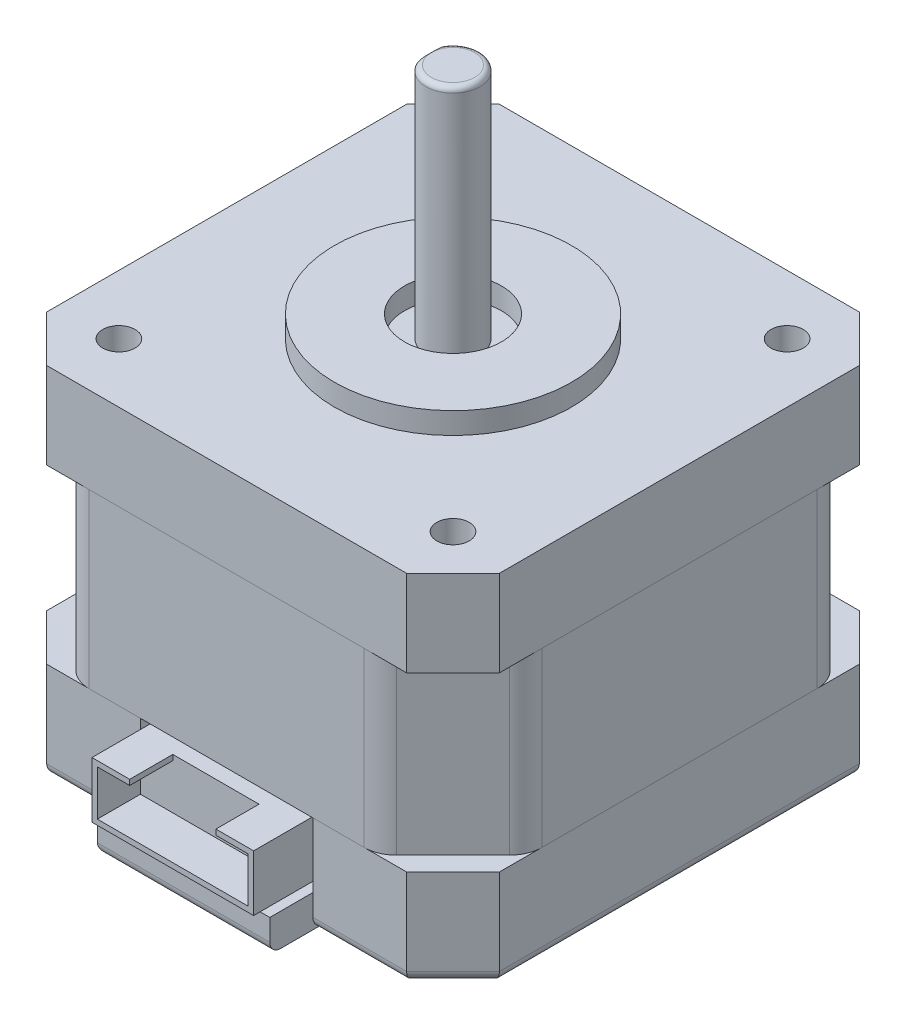
SolidWorks part; units mm, degrees
ref_plane "Front Plane" through (0, 0, 0) normal (0, 0, 1) x (1, 0, 0)
ref_plane "Top Plane" through (0, 0, 0) normal (0, 1, 0) x (1, 0, 0)
ref_plane "Right Plane" through (0, 0, 0) normal (1, 0, 0) x (0, 0, -1)
sketch "Sketch1" plane through (0, 0, 0) normal (0, 1, 0) x (1, 0, 0)
  line L0 (-21, 21) -> (21, -21) construction
  line L1 (-21, 21) -> (21, 21)
  line L2 (-21, 21) -> (-21, -21)
  line L3 (-21, -21) -> (21, -21)
  line L4 (21, 21) -> (21, -21)
  line L5 (-15.5, 15.5) -> (15.5, -15.5) construction
  circle A0 centre (-15.5, 15.5) radius 1.5
  circle A1 centre (15.5, 15.5) radius 1.5
  circle A2 centre (-15.5, -15.5) radius 1.5
  circle A3 centre (15.5, -15.5) radius 1.5
  point P4 (0, 0)
  point P14 (0, 0)
  dimension "D2" = 3
  dimension "D1" = 42
  dimension "D3" = 31
extrude "Boss-Extrude1" add sketch "Sketch1" along normal blind 8
sketch "Sketch2" plane through (0, 0, 0) normal (0, 1, 0) x (1, 0, 0)
  circle A0 centre (0, 0) radius 11
  circle A1 centre (0, 0) radius 4.5
  dimension "D1" = 22
  dimension "D2" = 9
extrude "Boss-Extrude2" add sketch "Sketch2" along normal blind 10
sketch "Sketch3" plane through (0, 0, 0) normal (0, 1, 0) x (1, 0, 0)
  line L0 (21, 21) -> (-21, -21) construction
  line L1 (-21, 21) -> (21, 21)
  line L2 (-21, 21) -> (-21, -21)
  line L3 (-21, -21) -> (21, -21)
  line L4 (21, 21) -> (21, -21)
  point P4 (0, 0)
  dimension "D1" = 42
extrude "Boss-Extrude3" add sketch "Sketch3" against normal blind 16 separate body
ref_plane "Plane1" through (0, -16, 0) normal (0, -1, 0) x (-1, 0, 0)
sketch "Sketch5" plane through (0, -16, 0) normal (0, -1, 0) x (-1, 0, 0)
  line L0 (21, 21) -> (-21, -21) construction
  line L1 (-21, 21) -> (21, 21)
  line L2 (-21, 21) -> (-21, -21)
  line L4 (21, 21) -> (21, -21)
  line L5 (1, 1) -> (-1, -1) construction
  line L6 (8, -21) -> (8, -1)
  line L7 (8, -1) -> (-8, -1)
  line L8 (-8, -1) -> (-8, -21)
  line L9 (21, -21) -> (8, -21)
  line L10 (21, -21) -> (-21, -21) construction
  line L11 (-8, -21) -> (-21, -21)
  point P4 (0, 0)
  point P13 (0, -1)
  point P15 (0, 0)
  dimension "D2" = 16
  dimension "D3" = 20
  dimension "D1" = 42
extrude "Boss-Extrude4" add sketch "Sketch5" along normal blind 9 separate body
chamfer "Chamfer1" distance 4.3 angle 45 4 edges at (-21, 4, -21) (21, 4, -21) (21, 4, 21) (-21, 4, 21)
chamfer "Chamfer5" distance 4.3 angle 45 4 edges at (21, -20.5, -21) (-21, -20.5, -21) (21, -20.5, 21) (-21, -20.5, 21)
chamfer "Chamfer6" distance 7 angle 45 4 edges at (-21, -8, -21) (21, -8, -21) (21, -8, 21) (-21, -8, 21)
fillet "Fillet1" radius 3 8 edges at (21, -8, 14) (14, -8, 21) (-14, -8, 21) (-21, -8, 14) (-21, -8, -14) (-14, -8, -21) (14, -8, -21) (21, -8, -14)
ref_plane "Plane5" through (0, -25, 0) normal (0, -1, 0) x (-1, 0, 0)
sketch "Sketch7" plane through (0, -25, -25) normal (0, 1, 0) x (1, 0, 0)
  line L0 (18.85, -6.15) -> (-18.85, -43.85) construction
  line L5 (16, -9) -> (-16, -41) construction
  line L7 (16.7, -4) -> (21, -8.3) construction
  line L8 (-16, -41) -> (-21, -41) construction
  line L9 (-21, -41.7) -> (-21, -8.3) construction
  line L10 (16, -9) -> (21, -9) construction
  line L11 (21, -8.3) -> (21, -41.7) construction
  line L12 (-16.7, -46) -> (-21, -41.7) construction
  circle A0 centre (16, -41) radius 2.75
  circle A1 centre (-16, -41) radius 2.75
  circle A2 centre (16, -9) radius 2.75
  circle A3 centre (-16, -9) radius 2.75
  point P6 (-18.85, -43.85)
  point P20 (18.85, -6.15)
  dimension "D2" = 32
  dimension "D3" = 5.5
extrude "Cut-Extrude3" cut sketch "Sketch7" along normal blind 3
sketch "Sketch8" plane through (0, -25, 0) normal (0, -1, 0) x (-1, 0, 0)
  line L0 (-16.7, -21) -> (-8, -21) construction
  line L1 (8, 0) -> (-8, 0)
  line L2 (8, 0) -> (8, -25)
  line L3 (8, -25) -> (-8, -25)
  line L4 (-8, 0) -> (-8, -25)
  point P4 (0, 0)
  dimension "D1" = 16
  dimension "D2" = 4
extrude "Boss-Extrude5" add sketch "Sketch8" against normal blind 3
fillet "Fillet2" radius 1 11 edges at (18.85, -25, -18.85) (0, -25, -21) (-18.85, -25, -18.85) (-21, -25, 0) (-18.85, -25, 18.85) (21, -25, 0) (18.85, -25, 18.85) (12.35, -25, 21) (-12.35, -25, 21) (-8, -25, 23) (0, -25, 25)
sketch "Sketch9" plane through (0, 0, 0) normal (0, 0, 1) x (1, 0, 0)
  line L0 (-7, -16.9) -> (-7, -21.1)
  line L2 (-7.5, -16.4) -> (-7.5, -21.6)
  line L3 (-7.5, -21.6) -> (7.5, -21.6)
  line L4 (7.5, -16.4) -> (7.5, -21.6)
  line L5 (-7, -21.1) -> (7, -21.1)
  line L6 (7, -21.1) -> (7, -16.9)
  line L8 (-7, -21.1) -> (-7, -21.6) construction
  line L9 (-7.5, -16.4) -> (-4, -16.4)
  line L10 (-4, -16.4) -> (-4, -16.9)
  line L11 (-4, -16.9) -> (-7, -16.9)
  line L12 (7.5, -16.4) -> (4, -16.4)
  line L13 (4, -16.4) -> (4, -16.9)
  line L14 (4, -16.9) -> (7, -16.9)
  line L15 (7, -21.1) -> (7.5, -21.1) construction
  point P10 (0, -21.6)
  dimension "D1" = 8
  dimension "D2" = 5.2
  dimension "D3" = 15
  dimension "D4" = 16.4
  dimension "D5" = 0.5
extrude "Boss-Extrude6" add sketch "Sketch9" along normal blind 26
sketch "Sketch10" plane through (0, -25, 0) normal (0, -1, 0) x (-1, 0, 0)
  circle A0 centre (0, 0) radius 4.5
  dimension "D1" = 9
extrude "Cut-Extrude4" cut sketch "Sketch10" against normal blind 2
sketch "Sketch11" plane through (0, -23, 0) normal (0, -1, 0) x (1, 0, 0)
  circle A0 centre (0, 0) radius 2
  circle A1 centre (0, 0) radius 2.5
  dimension "D1" = 4
  dimension "D2" = 5
extrude "Cut-Extrude5" cut sketch "Sketch11" against normal blind 0.5
fillet "Fillet3" radius 0.5 1 edges at (0, -23, -2)
fillet "Fillet4" radius 0.5 5 edges at (0, -25, -4.5) (16, -25, 18.75) (16, -25, -13.25) (-16, -25, -13.25) (-16, -25, 18.75)
sketch "Sketch12" plane through (0, -22, 0) normal (0, -1, 0) x (1, 0, 0)
  circle A0 centre (-16, 16) radius 2.5
  circle A1 centre (16, 16) radius 2.5
  circle A2 centre (-16, -16) radius 2.5
  circle A3 centre (16, -16) radius 2.5
  dimension "D1" = 5
extrude "Boss-Extrude7" add sketch "Sketch12" along normal blind 3
fillet "Fillet5" radius 2 4 edges at (16, -25, -18.5) (-16, -25, -18.5) (16, -25, 13.5) (-16, -25, 13.5)
sketch "Sketch13" plane through (0, -25, 0) normal (0, -1, 0) x (-1, 0, 0)
  line L0 (16.5, -14) -> (16.5, -15.5)
  line L1 (16.5, -15.5) -> (18, -15.5)
  line L2 (18, -15.5) -> (18, -16.5)
  line L3 (18, -16.5) -> (16.5, -16.5)
  line L4 (16.5, -16.5) -> (16.5, -18)
  line L5 (16.5, -18) -> (15.5, -18)
  line L6 (15.5, -18) -> (15.5, -16.5)
  line L7 (15.5, -16.5) -> (14, -16.5)
  line L8 (14, -16.5) -> (14, -15.5)
  line L9 (14, -15.5) -> (15.5, -15.5)
  line L10 (15.5, -15.5) -> (15.5, -14)
  line L11 (15.5, -14) -> (16.5, -14)
  line L12 (-15.5, -14) -> (-15.5, -15.5)
  line L13 (-15.5, -15.5) -> (-14, -15.5)
  line L14 (-14, -15.5) -> (-14, -16.5)
  line L15 (-14, -16.5) -> (-15.5, -16.5)
  line L16 (-15.5, -16.5) -> (-15.5, -18)
  line L17 (-15.5, -18) -> (-16.5, -18)
  line L18 (-16.5, -18) -> (-16.5, -16.5)
  line L19 (-16.5, -16.5) -> (-18, -16.5)
  line L20 (-18, -16.5) -> (-18, -15.5)
  line L21 (-18, -15.5) -> (-16.5, -15.5)
  line L22 (-16.5, -15.5) -> (-16.5, -14)
  line L23 (-16.5, -14) -> (-15.5, -14)
  line L24 (-15.5, 18) -> (-15.5, 16.5)
  line L25 (-15.5, 16.5) -> (-14, 16.5)
  line L26 (-14, 16.5) -> (-14, 15.5)
  line L27 (-14, 15.5) -> (-15.5, 15.5)
  line L28 (-15.5, 15.5) -> (-15.5, 14)
  line L29 (-15.5, 14) -> (-16.5, 14)
  line L30 (-16.5, 14) -> (-16.5, 15.5)
  line L31 (-16.5, 15.5) -> (-18, 15.5)
  line L32 (-18, 15.5) -> (-18, 16.5)
  line L33 (-18, 16.5) -> (-16.5, 16.5)
  line L34 (-16.5, 16.5) -> (-16.5, 18)
  line L35 (-16.5, 18) -> (-15.5, 18)
  line L36 (16.5, 18) -> (16.5, 16.5)
  line L37 (16.5, 16.5) -> (18, 16.5)
  line L38 (18, 16.5) -> (18, 15.5)
  line L39 (18, 15.5) -> (16.5, 15.5)
  line L40 (16.5, 15.5) -> (16.5, 14)
  line L41 (16.5, 14) -> (15.5, 14)
  line L42 (15.5, 14) -> (15.5, 15.5)
  line L43 (15.5, 15.5) -> (14, 15.5)
  line L44 (14, 15.5) -> (14, 16.5)
  line L45 (14, 16.5) -> (15.5, 16.5)
  line L46 (15.5, 16.5) -> (15.5, 18)
  line L47 (15.5, 18) -> (16.5, 18)
  circle A0 centre (16, -16) radius 0.7071 construction
  circle A1 centre (-16, -16) radius 0.7071 construction
  circle A2 centre (-16, 16) radius 0.7071 construction
  circle A3 centre (16, 16) radius 0.7071 construction
  circle A4 centre (16, 16) radius 0.5 construction
  dimension "D1" = 1
  dimension "D2" = 1.5
extrude "Cut-Extrude6" cut sketch "Sketch13" against normal blind 2
sketch "Sketch14" plane through (0, 0, 0) normal (0, 1, 0) x (1, 0, 0)
  circle A0 centre (0, 0) radius 2.5
  dimension "D1" = 5
extrude "Boss-Extrude8" add sketch "Sketch14" along normal blind 30
fillet "Fillet6" radius 0.5 1 edges at (0, 30, 2.5)
sketch "Sketch15" plane through (0, 30, 0) normal (0, 1, 0) x (1, 0, 0)
  line L1 (-4, 1.5) -> (-2, 1.5)
  line L2 (-4, 1.5) -> (-4, -1.5)
  line L3 (-4, -1.5) -> (-2, -1.5)
  line L4 (-2, 1.5) -> (-2, -1.5)
  circle A0 centre (0, 0) radius 2.5 construction
  point P4 (-2, 0)
  dimension "D2" = 5
  dimension "D1" = 3
  dimension "D3" = 2
extrude "Cut-Extrude7" cut sketch "Sketch15" against normal blind 18
sketch "Sketch16" plane through (0, 0, 0) normal (0, 0, 1) x (1, 0, 0)
  line L1 (-7.5, -16.4) -> (7.5, -16.4)
  line L2 (-7.5, -16.4) -> (-7.5, -21.6)
  line L3 (-7.5, -21.6) -> (7.5, -21.6)
  line L4 (7.5, -16.4) -> (7.5, -21.6)
extrude "Boss-Extrude9" add sketch "Sketch16" along normal blind 22
sketch "Esquisse1" plane through (0, 8, 0) normal (0, 1, 0) x (1, 0, 0)
  line L0 (-21, 0) -> (-42.6924, 0) construction
  line L1 (-21, 16.7) -> (-21, -16.7) construction
ref_axis "Axe1" through (-21, 8, 0) along (-1, 0, 0)
